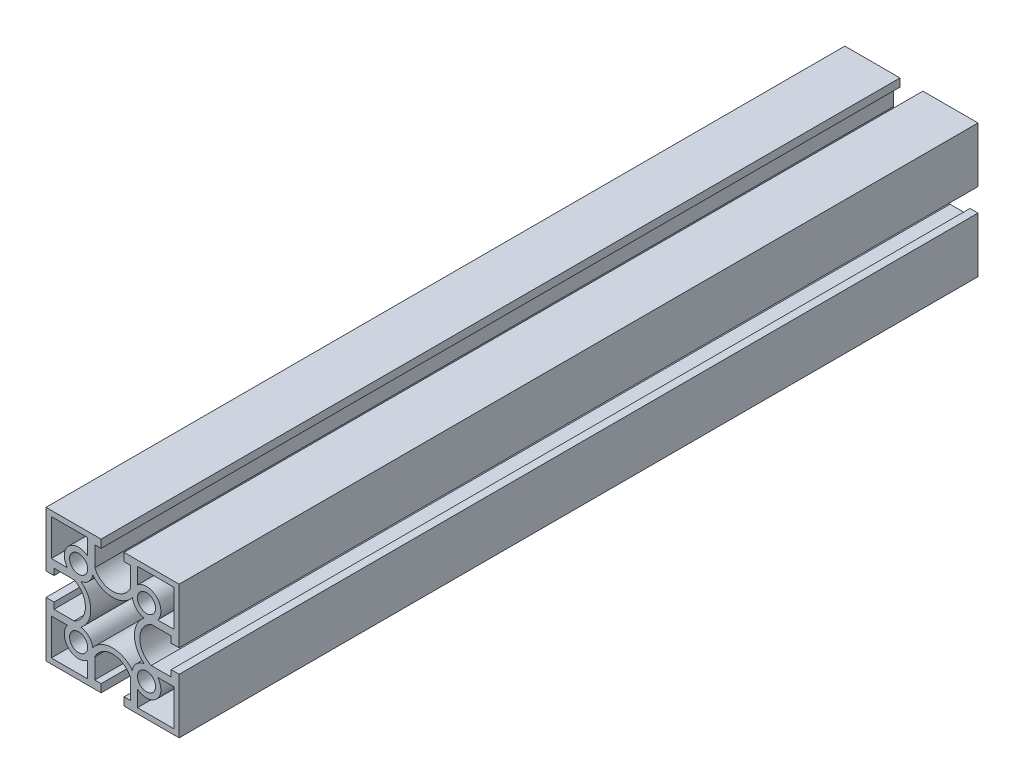
SolidWorks part; units mm, degrees
material "2024-O"
ref_plane "前基準面" through (0, 0, 0) normal (0, 0, 1) x (1, 0, 0)
ref_plane "上基準面" through (0, 0, 0) normal (0, 1, 0) x (1, 0, 0)
ref_plane "右基準面" through (0, 0, 0) normal (1, 0, 0) x (0, 0, -1)
sketch "草圖1" plane through (0, 0, 0) normal (0, 0, 1) x (1, 0, 0)
  line L0 (-26.0983, 0) -> (26.0983, 0) construction
  line L1 (0, -26.0995) -> (0, 26.0995) construction
  line L2 (4.3, 25) -> (25, 25)
  line L3 (25, 25) -> (25, 4.3)
  line L4 (25, 4.3) -> (22, 4.3)
  line L5 (22, 4.3) -> (22, 6.6873)
  line L6 (22, 6.6873) -> (14.5, 6.6873)
  line L7 (4.3, 25) -> (4.3, 22)
  line L8 (6.6873, 22) -> (6.6873, 14.5)
  line L9 (9.35, 23) -> (23, 23)
  line L10 (23, 23) -> (23, 9.35)
  line L11 (23, 9.35) -> (16.9452, 9.35)
  line L12 (9.35, 23) -> (9.35, 16.9452)
  line L13 (4.3, 22) -> (6.6873, 22)
  line L14 (23, 23) -> (23, 25) construction
  line L15 (23, 23) -> (25, 23) construction
  line L16 (18.9804, 25) -> (18.9804, 0) construction
  line L17 (25, 19.6172) -> (0, 19.6172) construction
  line L18 (8.2, -11.115) -> (8.2, 11.115) construction
  line L19 (-1.3349, 8.2958) -> (-1.0493, 10.2753) construction
  line L20 (10.6427, 6.3017) -> (12.1202, 4.9537) construction
  line L21 (12.75, 12.75) -> (12.75, 0) construction
  line L22 (12.75, 12.75) -> (0, 12.75) construction
  line L23 (0, 8.2) -> (4.3078, 8.2) construction
  line L24 (2.8556, 8.2) -> (2.8556, 0) construction
  line L25 (8.2, 4.4271) -> (0, 4.4271) construction
  line L27 (-4.3078, -8.2) -> (4.3078, -8.2) construction
  line L28 (12.75, -12.75) -> (-12.75, -12.75) construction
  line L29 (10.6427, -6.3017) -> (12.1202, -4.9537) construction
  line L30 (-1.3349, -8.2958) -> (-1.0493, -10.2753) construction
  line L31 (25, -19.6172) -> (-25, -19.6172) construction
  line L32 (23, -23) -> (25, -23) construction
  line L33 (23, -23) -> (23, -25) construction
  line L34 (4.3, -22) -> (6.6873, -22)
  line L35 (9.35, -23) -> (9.35, -16.9452)
  line L36 (23, -9.35) -> (16.9452, -9.35)
  line L37 (23, -23) -> (23, -9.35)
  line L38 (9.35, -23) -> (23, -23)
  line L39 (6.6873, -22) -> (6.6873, -14.5)
  line L40 (4.3, -25) -> (4.3, -22)
  line L41 (22, -6.6873) -> (14.5, -6.6873)
  line L42 (22, -4.3) -> (22, -6.6873)
  line L43 (25, -4.3) -> (22, -4.3)
  line L44 (25, -25) -> (25, -4.3)
  line L45 (4.3, -25) -> (25, -25)
  line L46 (-23, -23) -> (-23, -25) construction
  line L47 (-23, -23) -> (-25, -23) construction
  line L48 (1.3349, -8.2958) -> (1.0493, -10.2753) construction
  line L49 (-10.6427, -6.3017) -> (-12.1202, -4.9537) construction
  line L50 (-10.6427, 6.3017) -> (-12.1202, 4.9537) construction
  line L51 (1.3349, 8.2958) -> (1.0493, 10.2753) construction
  line L52 (-8.2, -11.115) -> (-8.2, 11.115) construction
  line L53 (-23, 23) -> (-25, 23) construction
  line L54 (-23, 23) -> (-23, 25) construction
  line L55 (-4.3, -25) -> (-25, -25)
  line L56 (-25, -25) -> (-25, -4.3)
  line L57 (-25, -4.3) -> (-22, -4.3)
  line L58 (-22, -4.3) -> (-22, -6.6873)
  line L59 (-22, -6.6873) -> (-14.5, -6.6873)
  line L60 (-4.3, -25) -> (-4.3, -22)
  line L61 (-6.6873, -22) -> (-6.6873, -14.5)
  line L62 (-9.35, -23) -> (-23, -23)
  line L63 (-23, -23) -> (-23, -9.35)
  line L64 (-23, -9.35) -> (-16.9452, -9.35)
  line L65 (-9.35, -23) -> (-9.35, -16.9452)
  line L66 (-4.3, -22) -> (-6.6873, -22)
  line L67 (-4.3, 22) -> (-6.6873, 22)
  line L68 (-9.35, 23) -> (-9.35, 16.9452)
  line L69 (-23, 9.35) -> (-16.9452, 9.35)
  line L70 (-23, 23) -> (-23, 9.35)
  line L71 (-9.35, 23) -> (-23, 23)
  line L72 (-6.6873, 22) -> (-6.6873, 14.5)
  line L73 (-4.3, 25) -> (-4.3, 22)
  line L74 (-22, 6.6873) -> (-14.5, 6.6873)
  line L75 (-22, 4.3) -> (-22, 6.6873)
  line L76 (-25, 4.3) -> (-22, 4.3)
  line L77 (-25, 25) -> (-25, 4.3)
  line L78 (-4.3, 25) -> (-25, 25)
  arc A0 (6.6873, 14.5) -> (-6.6873, 14.5) centre (0, 17.55) cw
  arc A1 (16.9452, 9.35) -> (9.35, 16.9452) centre (12.75, 12.75) ccw
  circle A2 centre (12.75, 12.75) radius 3.4
  arc A3 (14.5, -6.6873) -> (14.5, 6.6873) centre (17.55, 0) cw
  arc A4 (11.8648, 7.423) -> (11.8648, -7.423) centre (17.55, 0) ccw
  arc A5 (7.423, 11.8648) -> (-7.423, 11.8648) centre (0, 17.55) cw
  arc A6 (7.423, 11.8648) -> (11.8648, 7.423) centre (12.75, 12.75) ccw
  arc A7 (7.423, -11.8648) -> (11.8648, -7.423) centre (12.75, -12.75) cw
  arc A8 (7.423, -11.8648) -> (-7.423, -11.8648) centre (0, -17.55) ccw
  circle A9 centre (12.75, -12.75) radius 3.4
  arc A10 (16.9452, -9.35) -> (9.35, -16.9452) centre (12.75, -12.75) cw
  arc A11 (6.6873, -14.5) -> (-6.6873, -14.5) centre (0, -17.55) ccw
  arc A12 (-16.9452, -9.35) -> (-9.35, -16.9452) centre (-12.75, -12.75) ccw
  circle A13 centre (-12.75, -12.75) radius 3.4
  arc A14 (-7.423, -11.8648) -> (-11.8648, -7.423) centre (-12.75, -12.75) ccw
  arc A15 (-7.423, 11.8648) -> (-11.8648, 7.423) centre (-12.75, 12.75) cw
  arc A16 (-11.8648, 7.423) -> (-11.8648, -7.423) centre (-17.55, 0) cw
  arc A17 (-14.5, -6.6873) -> (-14.5, 6.6873) centre (-17.55, 0) ccw
  circle A18 centre (-12.75, 12.75) radius 3.4
  arc A19 (-16.9452, 9.35) -> (-9.35, 16.9452) centre (-12.75, 12.75) cw
  point P51 (2.8725, 0)
  point P55 (12.725, 0)
  point P63 (20.8598, 0)
  point P88 (0, -19.6172)
  point P93 (0, -12.75)
  point P95 (0, -2.988)
  point P96 (0, 2.988)
  point P106 (0, 0)
  point P137 (-20.8598, 0)
  point P138 (-12.725, 0)
  point P139 (-2.8725, 0)
  dimension "D4" = 2
  dimension "D8" = 2
  dimension "D9" = 6.8
  dimension "D1" = 25
  dimension "D2" = 8.6
  dimension "D3" = 3
  dimension "D5" = 2
  dimension "D6" = 7.5
  dimension "D7" = 8.2
  dimension "D10" = 25.5
extrude "本體" add sketch "草圖1" along normal mid plane 300
sketch "草圖2" [suppressed] plane through (25, 0, 0) normal (1, 0, 0) x (0, 0, -1)
  line L1 (-750, 4.3) -> (-750, 25) construction
  circle A0 centre (-736, 0) radius 4
  circle A2 centre (-736, 0) radius 14 construction
  dimension "D1" = 8
  dimension "D2" = 10
extrude "馬達架孔1" [suppressed] cut sketch "草圖2" against normal through all
pattern_linear "馬達架孔N" [suppressed] count 4 spacing 50 of bodies 102
